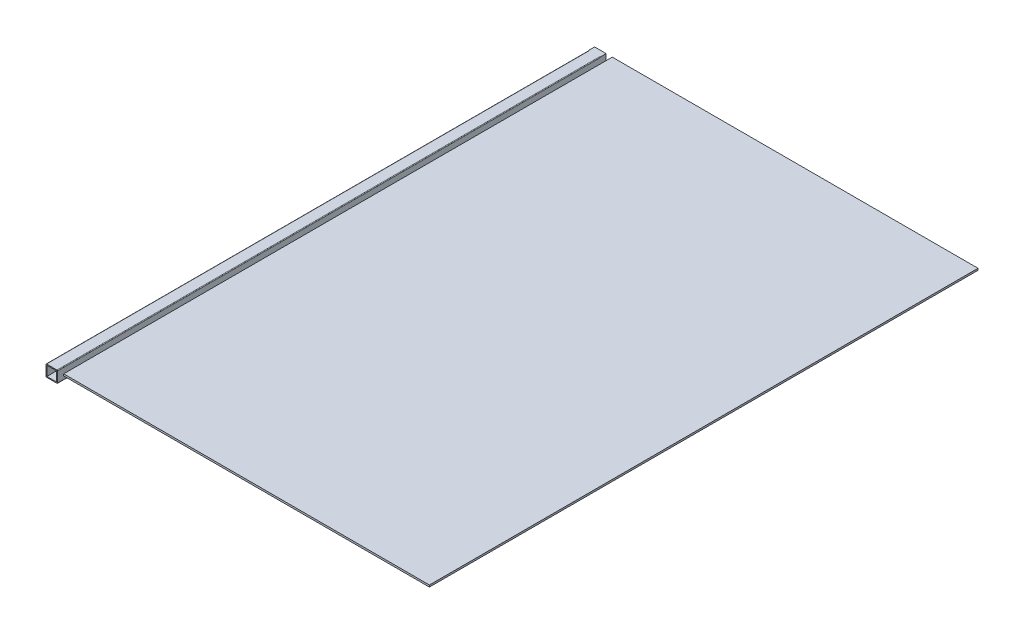
SolidWorks part; units mm, degrees
ref_plane "정면" through (0, 0, 0) normal (0, 0, 1) x (1, 0, 0)
ref_plane "윗면" through (0, 0, 0) normal (0, 1, 0) x (1, 0, 0)
ref_plane "우측면" through (0, 0, 0) normal (1, 0, 0) x (0, 0, -1)
sketch "스케치1" plane through (0, 0, 0) normal (0, 0, 1) x (1, 0, 0)
  line L1 (0, 0) -> (19, 0)
  line L2 (0, 0) -> (0, -19)
  line L3 (0, -19) -> (19, -19)
  line L4 (19, 0) -> (19, -19)
  line L5 (1.56, -1.56) -> (17.44, -1.56)
  line L6 (1.56, -1.56) -> (1.56, -17.44)
  line L7 (1.56, -17.44) -> (17.44, -17.44)
  line L8 (17.44, -1.56) -> (17.44, -17.44)
  line L9 (29, 0) -> (629, 0)
  line L10 (29, 0) -> (29, -3)
  line L11 (29, -3) -> (629, -3)
  line L12 (629, 0) -> (629, -3)
  dimension "D1" = 19
  dimension "D2" = 19
  dimension "D3" = 15.88
  dimension "D4" = 15.88
  dimension "D5" = 1.56
  dimension "D6" = 1.56
  dimension "D7" = 600
  dimension "D8" = 3
  dimension "D9" = 10
extrude "보스-돌출1" add sketch "스케치1" along normal blind 900
fillet "필렛2" radius 1 4 edges at (0, -19, 450) (0, 0, 450) (19, -19, 450) (19, 0, 450)
extrude "보스-돌출2" add sketch "스케치1<2>" along normal blind 10
sketch "스케치1<2>" plane through (0, 0, 0) normal (0, 0, 1) x (1, 0, 0) same geometry as "스케치1"
